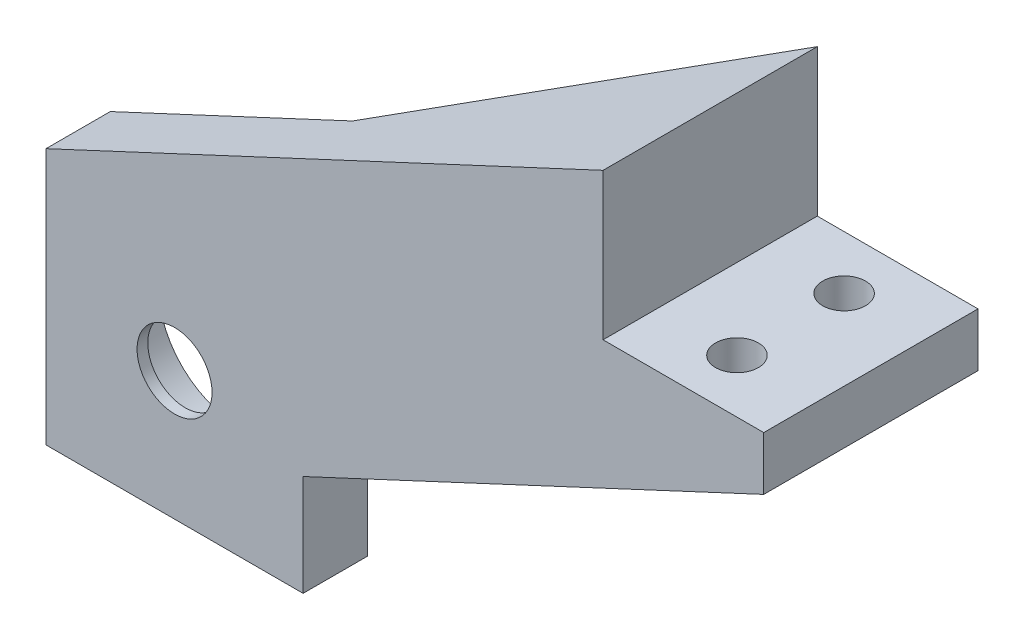
SolidWorks part; units mm, degrees
ref_plane "Front Plane" through (0, 0, 0) normal (0, 0, 1) x (1, 0, 0)
ref_plane "Top Plane" through (0, 0, 0) normal (0, 1, 0) x (1, 0, 0)
ref_plane "Right Plane" through (0, 0, 0) normal (1, 0, 0) x (0, 0, -1)
sketch "Sketch1" plane through (0, 0, 0) normal (0, 0, 1) x (1, 0, 0)
  circle A0 centre (0, 0) radius 7.5
  circle A1 centre (0, 0) radius 3.5
  circle A2 centre (0, 0) radius 10
  dimension "D1" = 15
  dimension "D2" = 20
  dimension "D3" = 7
extrude "Boss-Extrude1" add sketch "Sketch1" against normal up to surface (5 mm away) contours A2 A0 region at (-9.7172, 0, 0)
extrude "Boss-Extrude2" add sketch "Sketch1<3>" along normal blind 1 contours A0 A1 | A2 A0 region at (-7.2879, 0, 0) region at (-9.7172, 0, 0)
sketch "Sketch1<3>" plane through (0, 0, 0) normal (0, 0, 1) x (1, 0, 0) same geometry as "Sketch1"
sketch "Sketch2" plane through (0, 0, 1) normal (0, 0, 1) x (1, 0, 0)
  line L3 (55, 22.5) -> (40, 22.5)
  line L5 (-12, -0.9326) -> (-12, -12)
  line L6 (-12, -12) -> (12, -12)
  line L8 (40, 22.5) -> (40, 17.5)
  line L13 (40, 17.5) -> (55, 17.5)
  line L14 (55, 17.5) -> (55, 22.5)
  line L15 (-110, 22.5) -> (290, 22.5) construction
  line L16 (10.6203, 22.5) -> (-12, 11.952)
  line L17 (-12, -0.9326) -> (-12, 11.952)
  line L18 (40, 22.5) -> (10.6203, 22.5)
  line L19 (55, 17.5) -> (12, -2.5512)
  line L20 (12, -2.5512) -> (12, -12)
  line L21 (10.6203, 22.5) -> (40, 36.2)
  line L23 (34.1088, 37.8664) -> (-8.8309, 17.8433) construction
  line L24 (40, 22.5) -> (40, 34.2) construction
  line L25 (40, 36.2) -> (40, 22.5)
  circle A1 centre (0, 0) radius 10
  circle A2 centre (0, 0) radius 10 construction
  circle M4 centre (0, 0) radius 10
  dimension "D1" = 12
  dimension "D2" = 24
  dimension "D3" = 15
  dimension "D4" = 5
  dimension "D5" = 25
  dimension "D6" = 4
  dimension "D7" = 12
  dimension "D8" = 2
  dimension "D9" = 0
extrude "Boss-Extrude3" add sketch "Sketch2" against normal up to surface (6 mm away) contours L8 M4 | L6 L5 M4 | L8 | L25 L21 L18 region at (47.5, 20, 1) region at (16.0768, 9.8847, 1) region at (30.2068, 27.0667, 1) up to face at (-10, 0, -5)
sketch "Sketch3" plane through (0, 22.5, 0) normal (0, -1, 0) x (1, 0, 0)
  line L0 (40, -286) -> (40, 14) construction
  line L1 (55, -5) -> (40, -5)
  line L2 (55, -5) -> (55, -19)
  line L3 (55, -19) -> (40, -19)
  line L4 (40, -5) -> (40, -19)
  line L5 (55, -5) -> (40, -19) construction
  line L6 (55, -19) -> (40, -5) construction
  line L7 (55, 1) -> (12, 1) construction
  line L8 (40, -19) -> (10.6203, -5)
  line L9 (55, -5) -> (55, 1) construction
  line L10 (40, -5) -> (10.6203, -5)
  line L11 (40, -5) -> (-12, -5) construction
  point P4 (47.5, -12)
  point P11 (0, 0)
  point P14 (40, -19)
  point P16 (0, 0)
  dimension "D1" = 20
  dimension "D2" = 29.3797
extrude "Boss-Extrude7" add sketch "Sketch3" along normal up to surface (11.9946 mm away) contours L4 L10 L8 | L1 L4 L3 L2 region at (47.5, 22.5, -12) region at (30.2068, 22.5, -9.6667) up to face at (33.5, 7.4744, -2)
sketch "Sketch4" plane through (0, 22.5, 0) normal (0, -1, 0) x (1, 0, 0)
  line L1 (55, 1) -> (40, 1)
  line L2 (55, 1) -> (55, -19)
  line L3 (55, -19) -> (40, -19)
  line L4 (40, 1) -> (40, -19)
  line L5 (55, 1) -> (40, -19) construction
  line L6 (55, -19) -> (40, 1) construction
  line L7 (55, -19) -> (55, 1) construction
  line L8 (55, -9) -> (40, -9) construction
  line L9 (47.5, -9.9585) -> (44, -11.9793)
  line L10 (44, -11.9793) -> (44, -16.0207)
  line L11 (44, -16.0207) -> (47.5, -18.0415)
  line L12 (47.5, -18.0415) -> (51, -16.0207)
  line L13 (51, -16.0207) -> (51, -11.9793)
  line L14 (51, -11.9793) -> (47.5, -9.9585)
  line L21 (51, -6.0207) -> (47.5, -8.0415)
  line L22 (51, -1.9793) -> (51, -6.0207)
  line L23 (47.5, 0.0415) -> (51, -1.9793)
  line L24 (44, -1.9793) -> (47.5, 0.0415)
  line L25 (44, -6.0207) -> (44, -1.9793)
  line L26 (47.5, -8.0415) -> (44, -6.0207)
  line L27 (55, 1) -> (40, 1) construction
  circle A0 centre (47.5, -14) radius 3.5 construction
  circle A1 centre (47.5, -4) radius 3.5 construction
  circle A2 centre (47.5, -14) radius 2
  circle A3 centre (47.5, -4) radius 2
  point P4 (47.5, -9)
  point P28 (45.75, -10.9689)
  point P31 (0, 0)
  dimension "D3" = 4
  dimension "D1" = 7.5
  dimension "D2" = 7
  dimension "D4" = 5
  dimension "D5" = 15
  dimension "D6" = 20
extrude "Cut-Extrude4" cut sketch "Sketch4" along normal through all contours A2 | A3 region at (47.5, 22.5, -14) region at (47.5, 22.5, -4)
extrude "Cut-Extrude5" cut sketch "Sketch4<3>" along normal through all from offset 3 contours L26 L21 L22 L23 L24 L25 A3 | L13 L14 L9 L10 L11 L12 A2 region at (49.1965, 22.5, -11.0615) region at (49.1965, 22.5, -6.9385)
sketch "Sketch4<3>" plane through (0, 22.5, 0) normal (0, -1, 0) x (1, 0, 0) same geometry as "Sketch4"
extrude "Boss-Extrude8" add sketch "Sketch3<4>" against normal up to surface (13.7 mm away) contours L4 L10 L8 region at (30.2068, 22.5, -9.6667) up to face at (13.3241, 23.7608, -2.6)
sketch "Sketch3<4>" plane through (0, 22.5, 0) normal (0, -1, 0) x (1, 0, 0) same geometry as "Sketch3"
